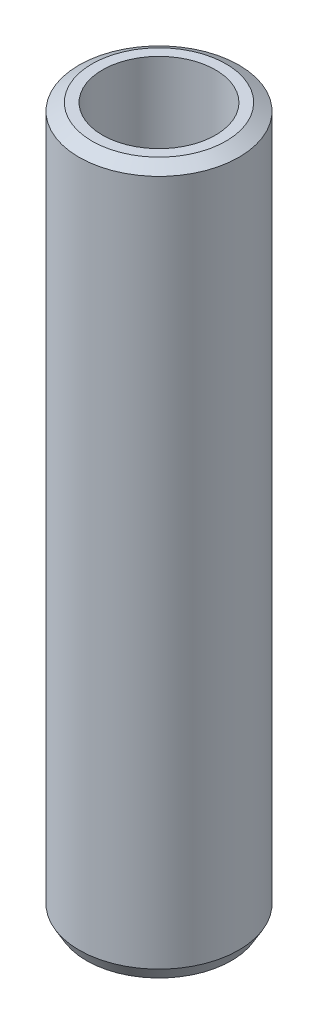
SolidWorks part; units mm, degrees
ref_plane "Front Plane" through (0, 0, 0) normal (0, 0, 1) x (1, 0, 0)
ref_plane "Top Plane" through (0, 0, 0) normal (0, 1, 0) x (1, 0, 0)
ref_plane "Right Plane" through (0, 0, 0) normal (1, 0, 0) x (0, 0, -1)
sketch "Sketch1" plane through (0, 0, 0) normal (0, 1, 0) x (1, 0, 0)
  circle A0 centre (0, 0) radius 52.5
  dimension "SHAFT_OD" = 105
extrude "Boss-Extrude1" add sketch "Sketch1" along normal blind 464.352
sketch "Sketch2" plane through (0, 0, 0) normal (0, 1, 0) x (1, 0, 0)
  circle A0 centre (0, 0) radius 37.1451
  dimension "BORE_D" = 74.2902
extrude "Cut-Extrude1" cut sketch "Sketch2" along normal through all
chamfer "Chamfer1" distance 4.9162 angle 60 2 edges at (0, 464.352, 52.5) (0, 0, 52.5) first distance on face at (0, 464.352, 52.5) first distance on face at (0, 0, 37.1451)
